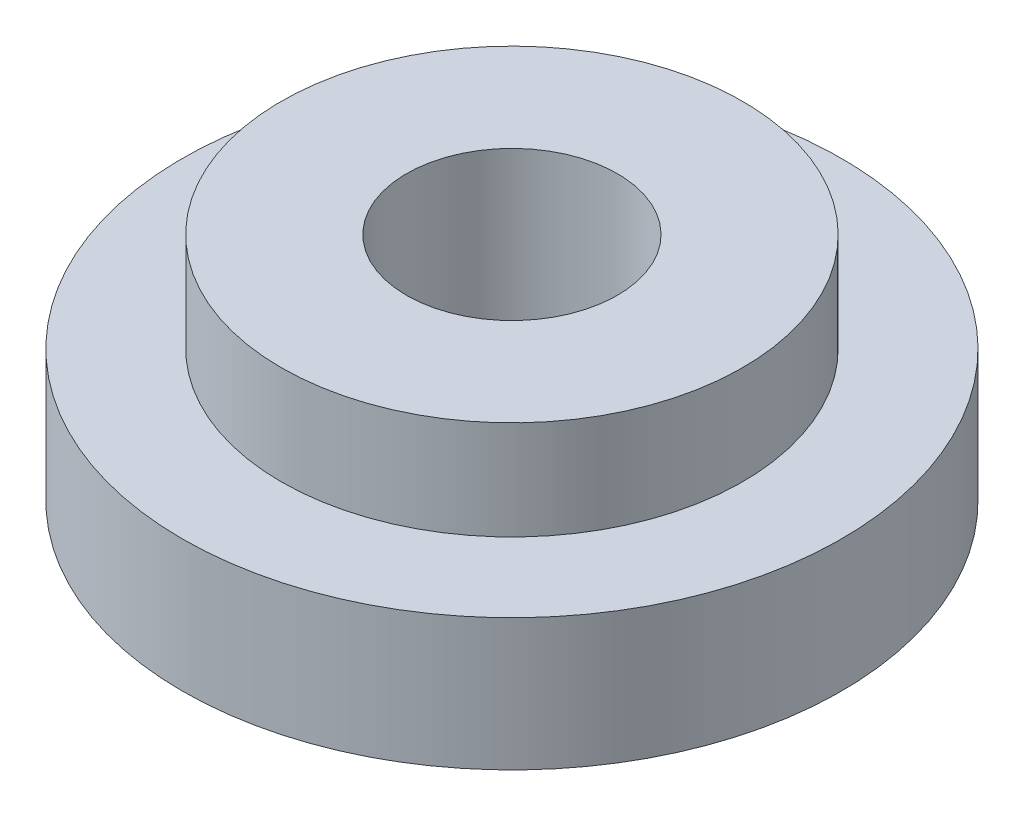
SolidWorks part; units mm, degrees
ref_plane "Front Plane" through (0, 0, 0) normal (0, 0, 1) x (1, 0, 0)
ref_plane "Top Plane" through (0, 0, 0) normal (0, 1, 0) x (1, 0, 0)
ref_plane "Right Plane" through (0, 0, 0) normal (1, 0, 0) x (0, 0, -1)
sketch "Sketch1" plane through (0, 0, 0) normal (0, 1, 0) x (1, 0, 0)
  circle A0 centre (0, 0) radius 5
  dimension "D1" = 10
extrude "Boss-Extrude1" add sketch "Sketch1" along normal blind 2
sketch "Sketch2" plane through (0, 2, 0) normal (0, 1, 0) x (1, 0, 0)
  circle A0 centre (0, 0) radius 3.5
  dimension "D1" = 7
extrude "Boss-Extrude2" add sketch "Sketch2" along normal blind 1.5
sketch "Sketch3" plane through (0, 3.5, 0) normal (0, 1, 0) x (1, 0, 0)
  circle A0 centre (0, 0) radius 1.6
  dimension "D1" = 3.2
extrude "Cut-Extrude1" cut sketch "Sketch3" against normal through all
